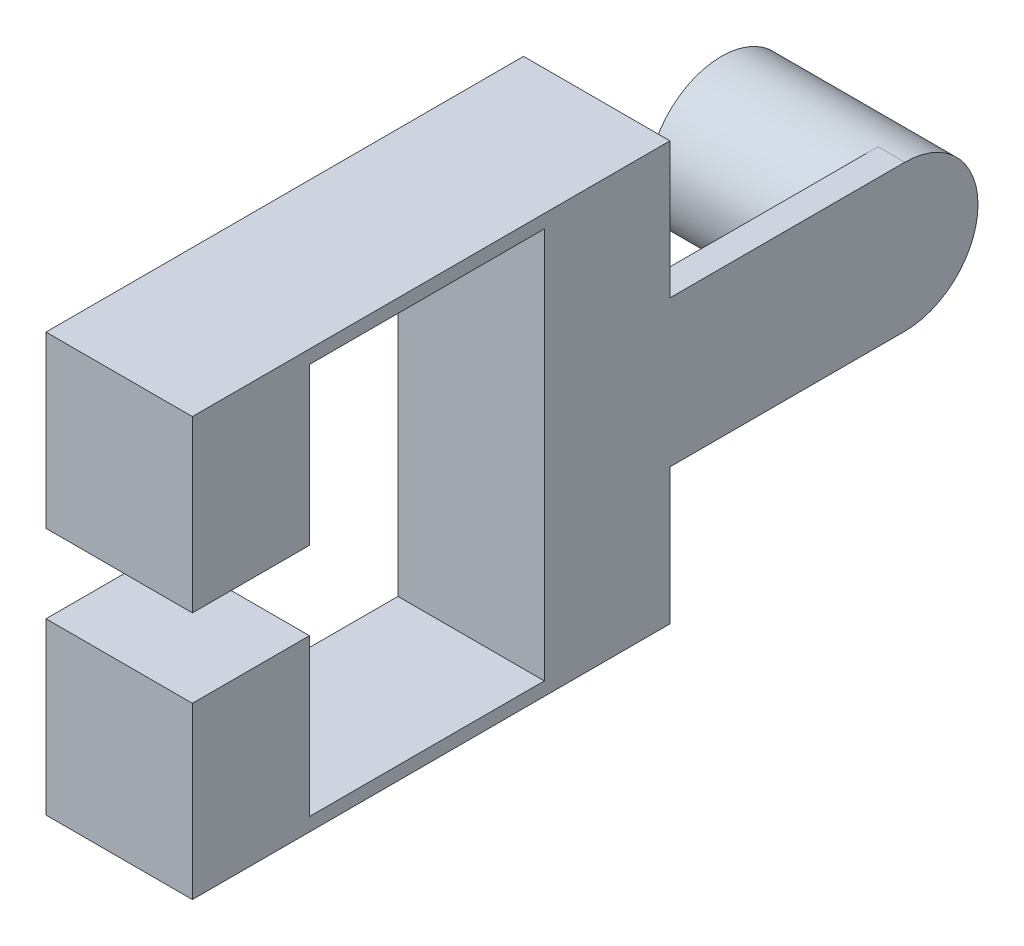
SolidWorks part; units mm, degrees
ref_plane "Front Plane" through (0, 0, 0) normal (1, 0, 0) x (0, 1, 0)
ref_plane "Top Plane" through (0, 0, 0) normal (0, 0, 1) x (0, 1, 0)
ref_plane "Right Plane" through (0, 0, 0) normal (0, 1, 0) x (-1, 0, 0)
sketch "Sketch1" plane through (0, 0, 0) normal (1, 0, 0) x (0, 1, 0)
  circle A0 centre (0, 0) radius 11.8736
  dimension "D1" = 23.7473
extrude "Boss-Extrude1" add sketch "Sketch1" along normal blind 25.4
sketch "Sketch2" plane through (25.4, 0, 0) normal (1, 0, 0) x (0, 1, 0)
  line L2 (-11.8736, 0) -> (-11.8736, 38.1)
  line L3 (-11.8736, 38.1) -> (11.8736, 38.1)
  line L4 (11.8736, 0) -> (11.8736, 38.1)
  circle A0 centre (0, 0) radius 11.8736 construction
  arc A1 (11.8736, 0) -> (-11.8736, 0) centre (0, 0) cw
  dimension "D1" = 38.1
  dimension "D2" = 23.7473
extrude "Boss-Extrude2" add sketch "Sketch2" along normal blind 4.3594
sketch "Sketch3" plane through (0, 0, 38.1) normal (0, 0, 1) x (1, 0, 0)
  line L0 (6.0121, 31.75) -> (29.7594, 31.75)
  line L1 (6.0121, 31.75) -> (6.0121, -31.75)
  line L2 (29.7594, 31.75) -> (29.7594, -31.75)
  line L3 (6.0121, -31.75) -> (29.7594, -31.75)
  line L7 (29.7594, 11.8736) -> (29.7594, -11.8736) construction
  line L8 (29.7594, 0) -> (-39.2285, 0) construction
  point P1 (29.7594, 0)
  dimension "D2" = 23.7473
extrude "Boss-Extrude3" add sketch "Sketch3" along normal blind 20.3772
sketch "Sketch6" plane through (0, 31.75, 0) normal (0, 1, 0) x (-1, 0, 0)
  line L0 (-29.7594, 58.4772) -> (-6.0121, 58.4772) construction
  line L1 (-29.7594, 38.1) -> (-6.0121, 38.1)
  line L2 (-29.7594, 38.1) -> (-29.7594, 96.5772)
  line L3 (-29.7594, 96.5772) -> (-6.0121, 96.5772)
  line L4 (-6.0121, 38.1) -> (-6.0121, 96.5772)
  dimension "D1" = 23.7473
  dimension "D2" = 38.1
extrude "Boss-Extrude4" add sketch "Sketch6" along normal blind 2.1797 contours L3 L4 L1 L2
sketch "Sketch7" plane through (0, -31.75, 0) normal (0, -1, 0) x (1, 0, 0)
  line L0 (29.7594, 58.4772) -> (6.0121, 58.4772) construction
  line L1 (29.7594, 38.1) -> (6.0121, 38.1)
  line L2 (29.7594, 38.1) -> (29.7594, 96.5772)
  line L3 (29.7594, 96.5772) -> (6.0121, 96.5772)
  line L4 (6.0121, 38.1) -> (6.0121, 96.5772)
  dimension "D1" = 23.7473
  dimension "D2" = 38.1
extrude "Boss-Extrude5" add sketch "Sketch7" along normal blind 2.1797
sketch "Sketch8" plane through (0, 0, 96.5772) normal (0, 0, 1) x (1, 0, 0)
  line L1 (6.0121, 33.9297) -> (29.7594, 33.9297)
  line L2 (6.0121, 33.9297) -> (6.0121, 6.35)
  line L3 (6.0121, 6.35) -> (29.7594, 6.35)
  line L4 (29.7594, 33.9297) -> (29.7594, 6.35)
  line L5 (29.7594, -31.75) -> (29.7594, 31.75) construction
  line L6 (6.0121, -33.9297) -> (29.7594, -33.9297)
  line L7 (6.0121, -33.9297) -> (6.0121, -6.35)
  line L8 (6.0121, -6.35) -> (29.7594, -6.35)
  line L9 (29.7594, -33.9297) -> (29.7594, -6.35)
  dimension "D1" = 27.5797
  dimension "D2" = 27.5797
extrude "Boss-Extrude6" add sketch "Sketch8" along normal blind 18.9918
equation "\"F\"= 800"
equation "\"P\"= 2 * \"F\""
equation "\"n\"= 4"
equation "\"Sy\"= 39885"
equation "\"Emod\"= 10007604"
equation "\"dmax\"= 0.005"
equation "\"l_A\"= 1"
equation "\"Z_A\"= \"n\" * \"P\" * \"l_A\" / ( 2 * \"Sy\" )"
equation "\"r_A\"= ( 4 * \"Z_A\" / pi ) ^ ( 1 / 3 )"
equation "\"d_A\"= 2 * \"r_A\""
equation "\"w\"= \"d_A\""
equation "\"L_B\"= 1.5"
equation "\"A_B\"= \"n\" * \"P\" / \"Sy\""
equation "\"t_B\"= \"A_B\" / \"w\""
equation "\"C\"= 2 * 1.0 + 0.5"
equation "\"M_C\"= \"P\" * \"C\" / 4"
equation "\"Z_C\"= \"n\" * \"M_C\" / \"Sy\""
equation "\"t_C\"= ( 6 * \"Z_C\" / \"w\" ) ^ ( 1 / 2 )"
equation "\"D\"= 1.5"
equation "\"P_D\"= \"P\" / 2"
equation "\"A_D\"= \"n\" * \"P_D\" / \"Sy\""
equation "\"t_D\"= \"A_D\" / \"w\""
equation "\"E_len\"= ( \"C\" - 0.5 ) / 2 + \"t_D\""
equation "\"M_E\"= \"P_D\" * \"E_len\""
equation "\"Z_E\"= \"n\" * \"M_E\" / \"Sy\""
equation "\"t_E\"= ( 6 * \"Z_E\" / \"w\" ) ^ ( 1 / 2 )"
equation "\"D1@Sketch1\"=\"r_A\" *2"
equation "\"D1@Boss-Extrude1\"=\"l_A\""
equation "\"D1@Sketch2\"=\"L_B\""
equation "\"D2@Sketch2\"=\"w\""
equation "\"D1@Boss-Extrude2\"=\"t_B\""
equation "\"D1@Sketch3\"=\"C\""
equation "\"D1@Boss-Extrude3\"=\"t_C\""
equation "\"D2@Sketch3\"=\"w\""
equation "\"D1@Sketch6\"=\"w\""
equation "\"D2@Sketch6\"=\"D\""
equation "\"D1@Boss-Extrude4\"=\"t_D\""
equation "\"D1@Sketch7\"=\"w\""
equation "\"D2@Sketch7\"=\"D\""
equation "\"D1@Boss-Extrude5\"=\"t_D\""
equation "\"D1@Sketch8\"=\"E_len\""
equation "\"D2@Sketch8\"=\"E_len\""
equation "\"D1@Boss-Extrude6\"=\"t_E\""
